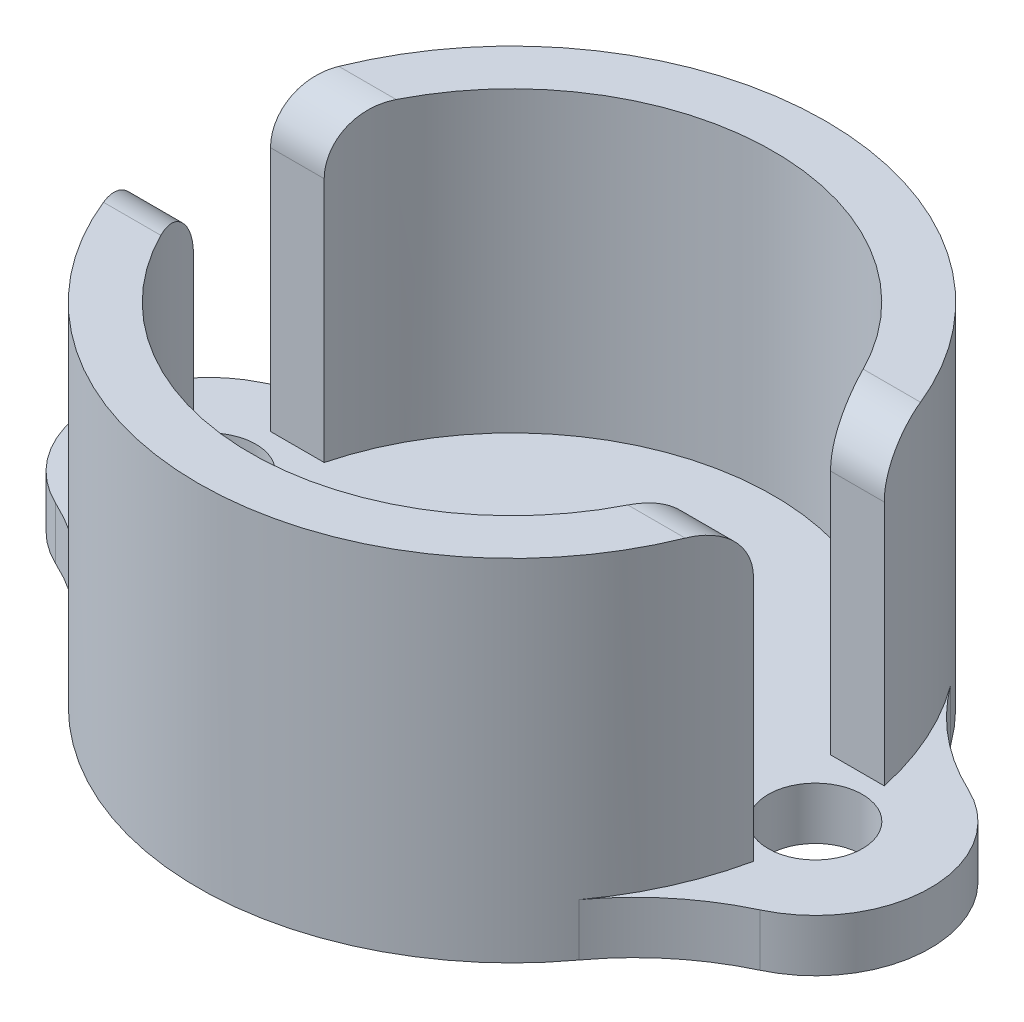
SolidWorks part; units mm, degrees
material "ABS"
ref_plane "Front" through (0, 0, 0) normal (0, 0, 1) x (1, 0, 0)
ref_plane "Top" through (0, 0, 0) normal (0, 1, 0) x (1, 0, 0)
ref_plane "Right" through (0, 0, 0) normal (1, 0, 0) x (0, 0, -1)
sketch "Sketch1" plane through (0, 0, 0) normal (0, 1, 0) x (1, 0, 0)
  line L0 (-7.366, 0) -> (7.366, 0) construction
  circle A0 centre (0, 0) radius 3.683
  circle A1 centre (7.366, 0) radius 1.143
  circle A2 centre (-7.366, 0) radius 1.143
  arc A3 (-7.0945, 2.7808) -> (-7.0945, -2.7808) centre (-7.366, 0) ccw
  arc A4 (7.0945, -2.7808) -> (7.0945, 2.7808) centre (7.366, 0) ccw
  circle A5 centre (0, 0) radius 6.35 construction
  arc A6 (-7.0945, -2.7808) -> (7.0945, -2.7808) centre (0, 0) ccw
  arc A7 (7.0945, 2.7808) -> (-7.0945, 2.7808) centre (0, 0) ccw
  point P9 (-10.16, 0)
  point P10 (10.16, 0)
  dimension "D2" = 2.286
  dimension "D4" = 12.7
  dimension "D5" = 15.24
  dimension "D6" = 7.366
  dimension "D1" = 14.732
  dimension "D3" = 20.32
extrude "Boss-Extrude1" add sketch "Sketch1" along normal blind 1.27
fillet "Fillet1" radius 6.35 4 edges at (7.0945, 0.635, -2.7808) (-7.0945, 0.635, -2.7808) (-7.0945, 0.635, 2.7808) (7.0945, 0.635, 2.7808)
sketch "Sketch2" plane through (0, 1.27, 0) normal (0, 1, 0) x (1, 0, 0)
  line L0 (0, 1.5875) -> (0, -1.5875) construction
  line L1 (-7.4528, 1.5875) -> (-6.1484, 1.5875)
  line L2 (-7.4528, -1.5875) -> (-6.1484, -1.5875)
  line L3 (6.1484, 1.5875) -> (7.4528, 1.5875)
  line L4 (6.1484, -1.5875) -> (7.4528, -1.5875)
  line L5 (-6.1484, 1.5875) -> (6.1484, 1.5875) construction
  line L6 (-6.1484, -1.5875) -> (6.1484, -1.5875) construction
  arc A0 (-7.4528, -1.5875) -> (7.4528, -1.5875) centre (0, 0) ccw
  arc A1 (6.139, 4.5141) -> (-6.139, 4.5141) centre (0, 0) ccw construction
  arc A2 (-6.1484, -1.5875) -> (6.1484, -1.5875) centre (0, 0) ccw
  arc A3 (6.1484, 1.5875) -> (-6.1484, 1.5875) centre (0, 0) ccw
  arc A4 (7.4528, 1.5875) -> (-7.4528, 1.5875) centre (0, 0) ccw
  arc M8 (-6.139, -4.5141) -> (6.139, -4.5141) centre (0, 0) ccw
  dimension "D1" = 12.7
  dimension "D2" = 3.175
extrude "Boss-Extrude2" add sketch "Sketch2" along normal blind 7.239 contours A2 L2 A0 L4 M8 | A3 L1 A4 L3 region at (-6.8006, 1.27, 1.7483)
sketch "Sketch3" plane through (0, 0, 0) normal (0, 0, 1) x (1, 0, 0)
  line L2 (-7.4528, 8.509) -> (-7.4528, 1.27) construction
  line L3 (7.4528, 8.509) -> (7.4528, 1.27) construction
  line L4 (-3.175, 6.35) -> (3.175, 6.35) construction
  line L5 (-6.139, 0) -> (6.139, 0) construction
  line L6 (0, 0) -> (0, 6.35) construction
  line L7 (-7.4528, 4.7625) -> (-7.4528, 8.509)
  line L8 (-7.4528, 8.509) -> (7.4528, 8.509)
  line L9 (7.4528, 8.509) -> (7.4528, 4.7625)
  spline S0 degree 3 poles (-7.4528, 4.7625) (-2.9413, 7.3077) (2.9413, 7.3077) (7.4528, 4.7625) knots 0 0 0 0 1 1 1 1
  dimension "D1" = 6.35
  dimension "D2" = 4.7625
  dimension "D3" = 6.35
extrude "Cut-Extrude1" [suppressed] cut sketch "Sketch3" against normal blind 25.4 and the other way blind 25.4 contours S0 L9 L8 L7
fillet "Fillet2" radius 1.27 4 edges at (6.8006, 8.509, -1.5875) (6.8006, 8.509, 1.5875) (-6.8006, 8.509, 1.5875) (-6.8006, 8.509, -1.5875)
